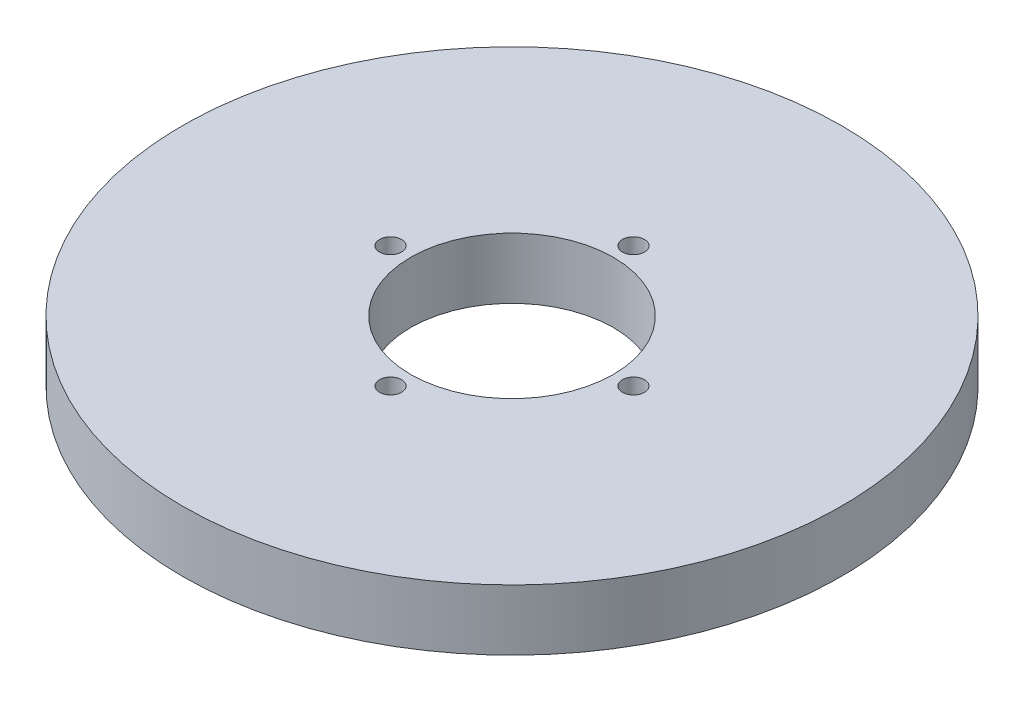
SolidWorks part; units mm, degrees
ref_plane "Front Plane" through (0, 0, 0) normal (0, 0, 1) x (1, 0, 0)
ref_plane "Top Plane" through (0, 0, 0) normal (0, 1, 0) x (1, 0, 0)
ref_plane "Right Plane" through (0, 0, 0) normal (1, 0, 0) x (0, 0, -1)
sketch "Sketch1" plane through (0, 0, 0) normal (0, 1, 0) x (1, 0, 0)
  circle A0 centre (0, 0) radius 97.5
  dimension "FLANGE_OD" = 195
extrude "Boss-Extrude1" add sketch "Sketch1" along normal blind 18
sketch "Sketch2" plane through (0, 0, 0) normal (0, 1, 0) x (1, 0, 0)
  circle A0 centre (0, 0) radius 30
  dimension "BORE_D" = 60
extrude "Cut-Extrude1" cut sketch "Sketch2" along normal through all
sketch "Sketch3" plane through (0, 18, 0) normal (0, 1, 0) x (1, 0, 0)
  circle A0 centre (0, 0) radius 35.9359 construction
  circle A1 centre (-35.9359, 0) radius 3.2544
  dimension "BOLT_D" = 6.5088
  dimension "BOLT_PCD" = 71.8718
extrude "Cut-Extrude2" cut sketch "Sketch3" against normal blind 15.0628
pattern_circular "CirPattern1" count 4 over 360 about axis through (0, 0, 0) along (0, 1, 0) of "Cut-Extrude2"
